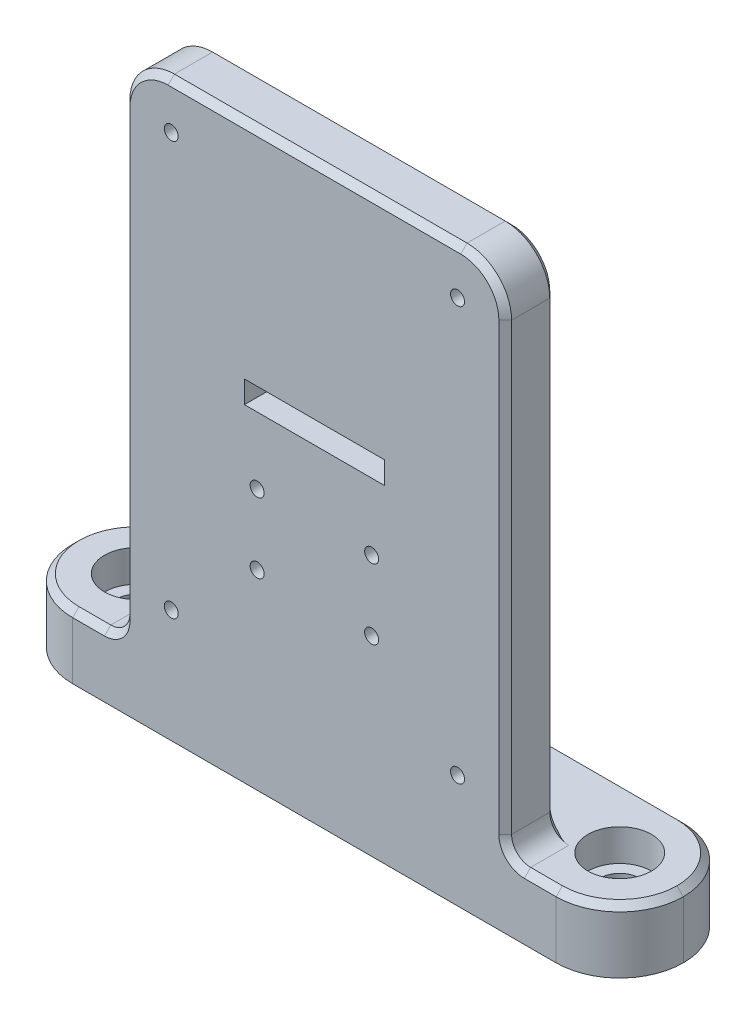
SolidWorks part; units mm, degrees
material "ABS"
ref_plane "前视基准面" through (0, 0, 0) normal (0, 0, 1) x (1, 0, 0)
ref_plane "上视基准面" through (0, 0, 0) normal (0, 1, 0) x (1, 0, 0)
ref_plane "右视基准面" through (0, 0, 0) normal (1, 0, 0) x (0, 0, -1)
sketch "草图1" plane through (0, 0, 0) normal (0, 1, 0) x (1, 0, 0)
  line L1 (-48, 10) -> (48, 10)
  line L2 (-48, 10) -> (-48, -10)
  line L3 (-48, -10) -> (48, -10)
  line L4 (48, 10) -> (48, -10)
  line L5 (-48, 10) -> (48, -10) construction
  line L6 (-48, -10) -> (48, 10) construction
  point P0 (0, 0)
extrude "凸台-拉伸1" add sketch "草图1" along normal blind 10 contours L2 L3 L4 L1
sketch "草图2" plane through (0, 10, 0) normal (0, 1, 0) x (1, 0, 0)
  line L0 (-48, 0) -> (-38, 0) construction
  line L1 (-48, 10) -> (-48, -10) construction
  line L2 (0, 0) -> (0, 10) construction
  line L3 (-48, 10) -> (48, 10) construction
  circle A0 centre (-38, 0) radius 5
  circle A1 centre (38, 0) radius 5
extrude "切除-拉伸1" cut sketch "草图2" against normal blind 5
fillet "圆角1" radius 10 4 edges at (48, 5, -10) (48, 5, 10) (-48, 5, 10) (-48, 5, -10)
sketch "草图3" plane through (0, 5, 0) normal (0, 1, 0) x (1, 0, 0)
  circle A0 centre (-38, 0) radius 3.1
  circle A1 centre (38, 0) radius 3.1
extrude "切除-拉伸2" cut sketch "草图3" against normal blind 5
chamfer "倒角1" distance 1 angle 45 2 edges at (38, 0, 3.1) (-38, 0, 3.1)
sketch "草图4" plane through (0, 10, 0) normal (0, 1, 0) x (1, 0, 0)
  line L0 (-38, 10) -> (38, 10) construction
  line L1 (-30, -10) -> (30, -10)
  line L2 (-30, -10) -> (-30, 10)
  line L3 (-30, 10) -> (30, 10)
  line L4 (30, -10) -> (30, 10)
  line L5 (-30, -10) -> (30, 10) construction
  line L6 (-30, 10) -> (30, -10) construction
  point P0 (0, 0)
extrude "凸台-拉伸2" add sketch "草图4" along normal blind 80
sketch "草图6" plane through (0, 0, 10) normal (0, 0, 1) x (1, 0, 0)
  line L0 (0, 0) -> (0, 90) construction
  line L1 (-30, 35.5) -> (30, 35.5) construction
  line L2 (-30, 90) -> (30, 90) construction
  line L3 (0, 90) -> (0, 35.5) construction
  line L4 (0, 30) -> (0, 4) construction
  line L5 (-2.5, 33.25) -> (2.5, 33.25) construction
  line L6 (-2.5, 33.25) -> (-2.5, 37.75) construction
  line L7 (-2.5, 37.75) -> (2.5, 37.75) construction
  line L8 (2.5, 33.25) -> (2.5, 37.75) construction
  line L9 (-2.5, 33.25) -> (2.5, 37.75) construction
  line L10 (-2.5, 37.75) -> (2.5, 33.25) construction
  line L11 (-9, 41) -> (9, 41) construction
  line L12 (-9, 41) -> (-9, 30) construction
  line L13 (-9, 30) -> (9, 30) construction
  line L14 (9, 41) -> (9, 30) construction
  line L15 (-9, 41) -> (9, 30) construction
  line L16 (-9, 30) -> (9, 41) construction
  line L17 (0, 4) -> (25, 4) construction
  line L18 (25, 4) -> (25, 74) construction
  line L19 (25, 74) -> (-25, 74) construction
  line L20 (-25, 74) -> (-25, 4) construction
  line L21 (-25, 4) -> (0, 4) construction
  line L22 (-25, 4) -> (-23.5, 4) construction
  line L23 (-23.5, 4) -> (-23.5, 5.5) construction
  line L24 (-25, 74) -> (-25, 72.5) construction
  line L25 (-25, 72.5) -> (-23.5, 72.5) construction
  line L26 (-23.5, 72.5) -> (-23.5, 5.5) construction
  line L27 (-23.5, 5.5) -> (23.5, 5.5) construction
  line L28 (23.5, 5.5) -> (23.5, 72.5) construction
  line L29 (23.5, 72.5) -> (-23.5, 72.5) construction
  line L30 (0, 41) -> (0, 55) construction
  line L31 (0, 55) -> (11, 55)
  line L32 (11, 55) -> (11, 51.5)
  line L33 (11, 51.5) -> (-11, 51.5)
  line L34 (-11, 51.5) -> (-11, 55)
  line L35 (-11, 55) -> (0, 55)
  line L41 (0, 74) -> (0, 4) construction
  line L42 (25, 39) -> (-25, 39) construction
  line L43 (-38, 0) -> (38, 0) construction
  circle A3 centre (-9, 41) radius 1.1
  circle A4 centre (9, 41) radius 1.1
  circle A5 centre (9, 30) radius 1.1
  circle A6 centre (-9, 30) radius 1.1
  point P126 (0, 39)
  dimension "D1" = 35.5
  dimension "D2" = 70
  dimension "D6" = 51.5
  dimension "D3" = 1.5
  dimension "D4" = 1.5
  dimension "D5" = 50
  dimension "D7" = 3.5
  dimension "D8" = 11
  dimension "D9" = 11
extrude "切除-拉伸4" cut sketch "草图6" against normal up to next contours A6 | A5 | A4 | A3
extrude "切除-拉伸5" cut sketch "草图6<8>" against normal blind 11 contours L35 L31 L32 L33 L34
sketch "草图6<8>" plane through (0, 0, 10) normal (0, 0, 1) x (1, 0, 0) same geometry as "草图6"
sketch "草图8" plane through (0, 0, -10) normal (0, 0, -1) x (-1, 0, 0)
  line L1 (-25, 4) -> (25, 4) construction
  line L2 (-25, 4) -> (-25, 74) construction
  line L3 (-25, 74) -> (25, 74) construction
  line L4 (25, 4) -> (25, 74) construction
  line L5 (0, 74) -> (0, 4) construction
  line L6 (-25, 39) -> (25, 39) construction
  line L7 (-30, -12) -> (30, -12)
  line L8 (-30, -12) -> (-30, 90)
  line L9 (-30, 90) -> (30, 90)
  line L10 (30, -12) -> (30, 90)
  line L11 (-30, -12) -> (30, 90) construction
  line L12 (-30, 90) -> (30, -12) construction
  point P4 (0, 39)
  point P148 (0, 39)
extrude "切除-拉伸6" cut sketch "草图8" against normal blind 12
sketch "草图9" plane through (0, 0, 2) normal (0, 0, -1) x (-1, 0, 0)
  circle A0 centre (-22.5, 82.7979) radius 1.1
  circle A1 centre (22.5, 82.7979) radius 1.1
  circle A2 centre (22.5, 17.7979) radius 1.1
  circle A3 centre (-22.5, 17.7979) radius 1.1
extrude "切除-拉伸7" cut sketch "草图9" against normal blind 10
fillet "圆角8" radius 7 2 edges at (-30, 90, 6) (30, 90, 6)
sketch "草图10" plane through (30, 0, 0) normal (-1, 0, 0) x (0, 0, 1)
  line L1 (-10, 10) -> (2, 10)
  line L2 (-10, 10) -> (-10, 0)
  line L3 (-10, 0) -> (2, 0)
  line L4 (2, 10) -> (2, 0)
  line L5 (-4, 0) -> (-4, 10) construction
  line L6 (-10, 5) -> (2, 5) construction
  point P84 (-4, 5)
extrude "凸台-拉伸3" add sketch "草图10" along normal up to surface (60 mm away) up to face at (-30, 5, -4)
fillet "圆角11" radius 3 2 edges at (-30, 10, 6) (30, 10, 6)
chamfer "倒角4" distance 1 angle 45 21 edges at (-30, 48, 2) (-27.9497, 87.9497, 2) (0, 90, 2) (27.9497, 87.9497, 2) (30, 48, 2) (-45.0711, 10, -7.0711) (0, 10, -10) (-45.0711, 10, 7.0711) (45.0711, 10, -7.0711) (-35.5, 10, 10) (45.0711, 10, 7.0711) (-30.8787, 10.8787, 10) (35.5, 10, 10) (-30, 48, 10) (30.8787, 10.8787, 10) (-27.9497, 87.9497, 10) (30, 48, 10) (0, 90, 10) (27.9497, 87.9497, 10) (-30.8787, 10.8787, 2) (30.8787, 10.8787, 2)
